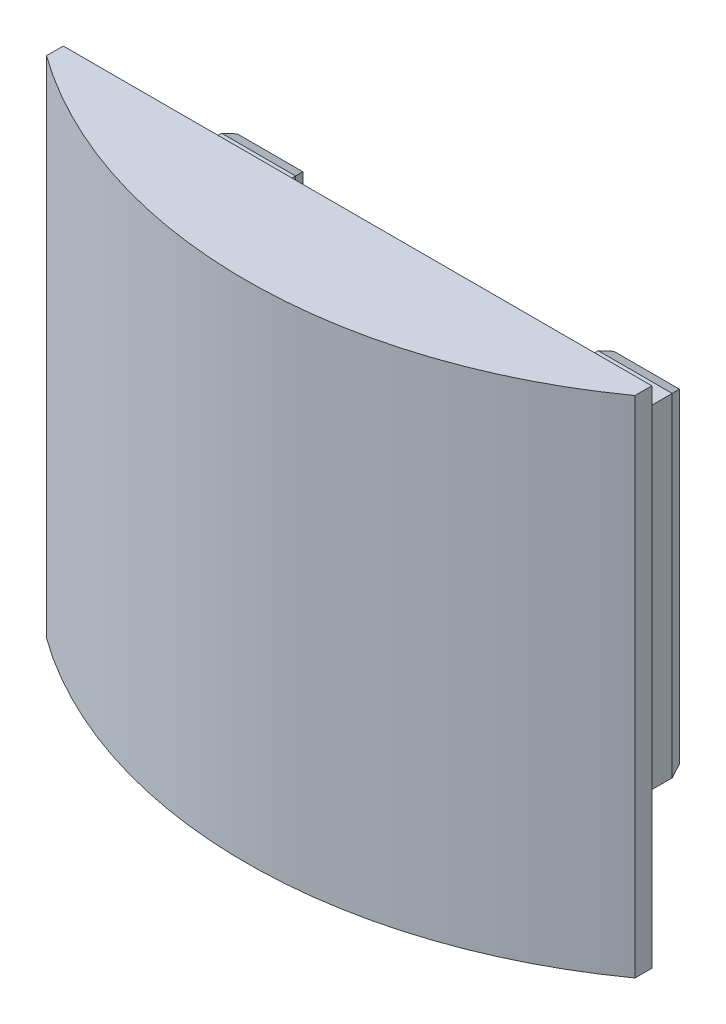
SolidWorks part; units mm, degrees
ref_plane "Спереди" through (0, 0, 0) normal (0, 0, 1) x (1, 0, 0)
ref_plane "Сверху" through (0, 0, 0) normal (0, 1, 0) x (1, 0, 0)
ref_plane "Справа" through (0, 0, 0) normal (1, 0, 0) x (0, 0, -1)
sketch "Sketch2" plane through (0, 0, 0) normal (0, 0, 1) x (1, 0, 0)
  line L1 (26.8, -19.8) -> (-26.8, -19.8)
  line L2 (26.8, -19.8) -> (26.8, 19.8)
  line L3 (26.8, 19.8) -> (-26.8, 19.8)
  line L4 (-26.8, -19.8) -> (-26.8, 19.8)
  line L5 (26.8, -19.8) -> (-26.8, 19.8) construction
  line L6 (26.8, 19.8) -> (-26.8, -19.8) construction
  point P0 (0, 0)
  dimension "D1" = 53.6
  dimension "D2" = 39.6
extrude "Boss-Extrude1" add sketch "Sketch2" along normal blind 12
sketch "Sketch3" plane through (0, 0, 12) normal (0, 0, 1) x (1, 0, 0)
  line L0 (0, 19.8) -> (0, -19.8) construction
  line L1 (35, -30) -> (-35, -30)
  line L2 (35, -30) -> (35, 30)
  line L3 (35, 30) -> (-35, 30)
  line L4 (-35, -30) -> (-35, 30)
  line L5 (35, -30) -> (-35, 30) construction
  line L6 (35, 30) -> (-35, -30) construction
  line L7 (26.8, 19.8) -> (-26.8, 19.8) construction
  line L8 (-26.8, -19.8) -> (26.8, -19.8) construction
  point P0 (0, 0)
  point P7 (0, 0)
  dimension "D1" = 70
  dimension "D2" = 60
  dimension "D3" = 0
extrude "Boss-Extrude2" add sketch "Sketch3" along normal blind 31.5
sketch "Sketch4" plane through (0, 19.8, 0) normal (0, 1, 0) x (1, 0, 0)
  line L0 (26.8, -4.6) -> (-26.8, -4.6) construction
  line L1 (26.8, -12) -> (26.8, 0) construction
  line L2 (-26.8, -12) -> (-26.8, 0) construction
  line L3 (26.8, -12) -> (-26.8, -12) construction
  circle A0 centre (22.5, -4.6) radius 2.1
  circle A1 centre (-22.5, -4.6) radius 2.1
  point P12 (0, -4.6)
  dimension "D2" = 4.2
  dimension "D3" = 4.2
  dimension "D1" = 7.4
  dimension "D4" = 45
  dimension "D5" = 22.5
extrude "Cut-Extrude1" cut sketch "Sketch4" against normal through all
sketch "Sketch5" plane through (0, 0, 0) normal (0, 0, -1) x (-1, 0, 0)
  line L0 (-26.8, 19.8) -> (26.8, 19.8) construction
  line L1 (18, -19.8) -> (-18, -19.8)
  line L2 (18, -19.8) -> (18, 19.8)
  line L3 (18, 19.8) -> (-18, 19.8)
  line L4 (-18, -19.8) -> (-18, 19.8)
  line L5 (18, -19.8) -> (-18, 19.8) construction
  line L6 (18, 19.8) -> (-18, -19.8) construction
  point P0 (0, 0)
  dimension "D1" = 36
extrude "Cut-Extrude2" cut sketch "Sketch5" against normal up to surface (12 mm away) up to face at (0, 0, 12)
chamfer "Chamfer1" distance 0.5 angle 70 8 edges at (26.8, 0, 0) (22.4, 19.8, 0) (18, 0, 0) (22.4, -19.8, 0) (-26.8, 0, 0) (-22.4, -19.8, 0) (-18, 0, 0) (-22.4, 19.8, 0) first distance on face at (22.4, 0, 0) first distance on face at (-22.4, 0, 0)
sketch "Sketch27" plane through (0, -30, 0) normal (0, -1, 0) x (1, 0, 0)
  line L0 (-35, 43.5) -> (-35, 12) construction
  line L1 (35, 43.5) -> (35, 12) construction
  line L2 (-35, 14) -> (-35, 12) construction
  line L3 (-35, 12) -> (35, 12) construction
  line L4 (35, 12) -> (35, 14) construction
  arc A0 (-35, 14) -> (35, 14) centre (0, -34.734) cw
  arc A1 (-35, 14) -> (35, 14) centre (0, 72.1657) cw
  dimension "D2" = 60
  dimension "D1" = 2
extrude "Cut-Extrude13" cut sketch "Sketch27" against normal through all
